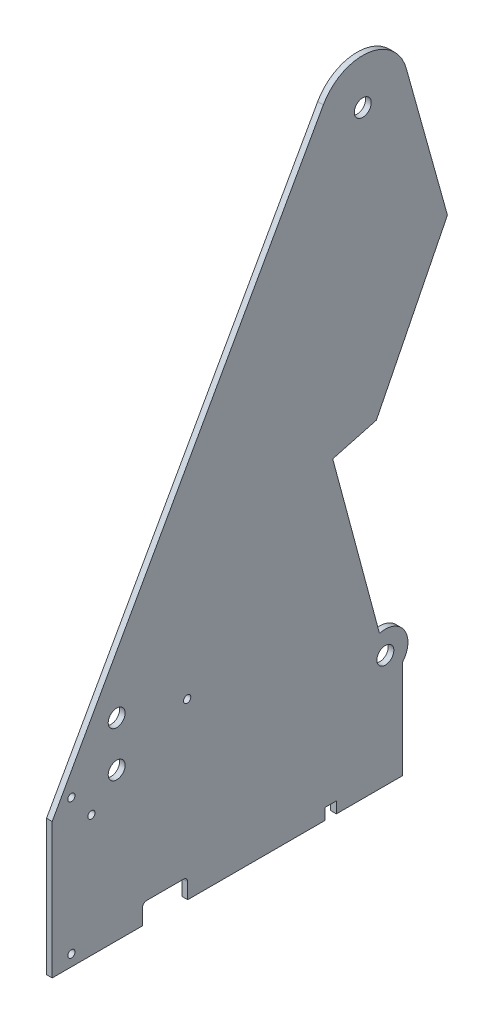
SolidWorks part; units mm, degrees
ref_plane "Front Plane" through (0, 0, 0) normal (0, 0, 1) x (1, 0, 0)
ref_plane "Top Plane" through (0, 0, 0) normal (0, 1, 0) x (1, 0, 0)
ref_plane "Right Plane" through (0, 0, 0) normal (1, 0, 0) x (0, 0, -1)
sketch "Sketch1" plane through (0, 0, 0) normal (1, 0, 0) x (0, 0, -1)
  line L0 (0, 0) -> (0, 55.0997)
  line L6 (-39.108, 173.9053) -> (-14.5735, 180.4793)
  line L7 (-14.5735, 180.4793) -> (25.4, 260.35)
  line L8 (25.4, 260.35) -> (2.241, 343.3746)
  line L9 (-44.3964, 348.943) -> (-196.85, 76.2)
  line L10 (-196.85, 0) -> (0, 0)
  line L11 (-196.85, 76.2) -> (-196.85, 0)
  line L13 (-39.108, 173.9053) -> (-12.812, 75.7673)
  line L14 (-12.812, 75.7673) -> (13.738, 82.8813) construction
  arc A0 (2.241, 343.3746) -> (-44.3964, 348.943) centre (-22.225, 336.55) ccw
  arc A3 (0, 55.0997) -> (-12.812, 75.7673) centre (-9.525, 63.5) ccw
  dimension "D2" = 25.4
  dimension "D6" = 196.85
  dimension "D7" = 76.2
  dimension "D12" = 12.7
  dimension "D1" = 22.225
  dimension "D3" = 336.55
  dimension "D4" = 25.4
  dimension "D5" = 101.6
  dimension "D10" = 9.525
  dimension "D11" = 63.5
  dimension "D13" = 76.2
  dimension "D14" = 25.4
  dimension "D15" = 15
extrude "Boss-Extrude1" add sketch "Sketch1" along normal blind 3.175
sketch "Sketch2" plane through (3.175, 0, 0) normal (1, 0, 0) x (0, 0, -1)
  line L16 (-146.05, 8.7909) -> (-146.05, -0.3034) construction
  line L17 (-123.0376, 11.1785) -> (-143.6624, 11.1785) construction
  line L18 (-120.65, -0.3034) -> (-120.65, 8.7909) construction
  line L19 (-146.05, 8.7909) -> (-146.05, 0)
  line L20 (-123.0376, 11.1785) -> (-143.6624, 11.1785)
  line L21 (-120.65, 0) -> (-120.65, 8.7909)
  line L23 (-37.0504, 0) -> (-37.0504, 6.35) construction
  line L24 (-43.4004, 0) -> (-37.0504, 0) construction
  line L25 (-146.05, 0) -> (-120.65, 0)
  line L26 (-196.85, 0) -> (0, 0) construction
  line L27 (-43.4004, 6.35) -> (-43.4004, 0) construction
  line L28 (-37.0504, 6.35) -> (-43.4004, 6.35) construction
  line L29 (-37.0504, 0) -> (-37.0504, 6.35)
  line L30 (-43.4004, 0) -> (-37.0504, 0)
  line L31 (-43.4004, 6.35) -> (-43.4004, 0)
  line L32 (-37.0504, 6.35) -> (-43.4004, 6.35)
  line L33 (-223.2996, 0) -> (-223.2996, 6.35) construction
  line L34 (-229.6496, 0) -> (-223.2996, 0) construction
  line L35 (-229.6496, 6.35) -> (-229.6496, 0) construction
  line L36 (-223.2996, 6.35) -> (-229.6496, 6.35) construction
  line L37 (-223.2996, 0) -> (-223.2996, 6.35)
  line L38 (-229.6496, 0) -> (-223.2996, 0)
  line L39 (-229.6496, 6.35) -> (-229.6496, 0)
  line L40 (-223.2996, 6.35) -> (-229.6496, 6.35)
  arc A0 (-143.6624, 11.1785) -> (-146.05, 8.7909) centre (-143.6624, 8.7909) ccw construction
  arc A1 (-120.65, 8.7909) -> (-123.0376, 11.1785) centre (-123.0376, 8.7909) ccw construction
  arc A2 (-143.6624, 11.1785) -> (-146.05, 8.7909) centre (-143.6624, 8.7909) ccw
  arc A3 (-120.65, 8.7909) -> (-123.0376, 11.1785) centre (-123.0376, 8.7909) ccw
extrude "Cut-Extrude1" cut sketch "Sketch2" against normal through all
sketch "Sketch3" plane through (3.175, 0, 0) normal (1, 0, 0) x (0, 0, -1)
  point P0 (-22.225, 336.55)
  point P4 (-9.525, 63.5)
hole_wizard "3/8 Clearance Hole1" positions "Sketch3" profile "Sketch4" hole size "3/8" standard "ANSI Inch" end condition up to next
sketch "Sketch4" plane through (3.175, 336.55, 22.225) normal (0, 1, 0) x (0, 0, -1)
  line L0 (0, 0) -> (0, 3.175)
  line L1 (0, 3.175) -> (4.7625, 3.175)
  line L2 (4.7625, 3.175) -> (4.7625, 0)
  line L5 (4.7625, 0) -> (0, 0)
  line L11 (0, -6.35) -> (0, 107.95) construction
  dimension "Thru Hole Dia." = 9.525
  dimension "Thru Hole Depth" = 3.175
sketch "Sketch5" [suppressed] plane through (3.175, 0, 0) normal (1, 0, 0) x (0, 0, -1)
  line L0 (-9.525, 63.5) -> (26.2895, 27.4728)
  line L1 (26.2895, 27.4728) -> (26.2524, 14.9296)
  line L2 (21.8127, 31.9762) -> (-24.8224, 22.3166)
  line L3 (-15.875, 19.05) -> (-24.8224, 22.3166)
  line L4 (0, 0) -> (0, 55.0997) construction
  line L5 (-15.875, 19.05) -> (-33.1481, 11.0161)
  line L6 (-33.1481, 11.0161) -> (-54.7505, 169.5016)
  line L7 (50.8, 0) -> (50.8, 73.5762) construction
  dimension "D1" = 44.45
  dimension "D2" = 50.8
  dimension "D3" = 45
  dimension "D4" = 60.325
  dimension "D5" = 19.05
  dimension "D6" = 15.875
  dimension "D7" = 9.525
  dimension "D8" = 47.625
  dimension "D9" = 19.05
  dimension "D10" = 45
  dimension "D11" = 50.8
sketch "Sketch6" plane through (3.175, 0, 0) normal (1, 0, 0) x (0, 0, -1)
  line L1 (-160.5832, 108.5458) -> (-174.4403, 116.2915) construction
  line L3 (-44.3964, 348.943) -> (-196.85, 76.2) construction
  circle A2 centre (-160.5832, 108.5458) radius 4.7625
  dimension "D4" = 9.525
  dimension "D5" = 15.875
  dimension "D6" = 266.7
extrude "Cut-Extrude2" cut sketch "Sketch6" against normal through all
sketch "Sketch8" plane through (3.175, 0, 0) normal (1, 0, 0) x (0, 0, -1)
  circle A0 centre (-160.5832, 83.1458) radius 4.7625
  circle A1 centre (-174.8072, 68.4138) radius 2.032
  circle A2 centre (-120.9592, 97.8778) radius 2.032
  circle A3 centre (-174.8072, 68.4138) radius 1.905 construction
  circle A4 centre (-120.9592, 97.8778) radius 1.985 construction
  dimension "D1" = 25.4
  dimension "D2" = 9.525
  dimension "D3" = 4.064
extrude "Cut-Extrude3" cut sketch "Sketch8" against normal through all both and the other way through all
sketch "Sketch9" plane through (3.175, 0, 0) normal (1, 0, 0) x (0, 0, -1)
  circle A8 centre (-174.8072, 68.4138) radius 4.445
  circle A9 centre (-174.8072, 68.4138) radius 4.445
  dimension "D1" = 2.54
sketch "Sketch10" [suppressed] plane through (3.175, 0, 0) normal (1, 0, 0) x (0, 0, -1)
  circle A0 centre (-71.2566, 151.9429) radius 2.032
  dimension "D1" = 4.064
extrude "Cut-Extrude4" [suppressed] cut sketch "Sketch10" against normal through all
sketch "Sketch11" plane through (3.175, 0, 0) normal (1, 0, 0) x (0, 0, -1)
  circle A0 centre (-186.055, 82.4979) radius 2.032
  circle A1 centre (-186.055, 6.35) radius 2.032
  circle A2 centre (-186.055, 6.35) radius 2.032 construction
  circle A3 centre (-186.055, 82.4979) radius 2.032 construction
  dimension "D1" = 4.064
extrude "Cut-Extrude5" cut sketch "Sketch11" against normal through all
sketch "Sketch13" [suppressed] plane through (0, 0, 0) normal (-1, 0, 0) x (0, 0, 1)
  circle A0 centre (31.5283, 339.7286) radius 2.032
  circle A1 centre (36.1757, 331.4144) radius 2.032
  dimension "D1" = 4.064
extrude "Cut-Extrude6" [suppressed] cut sketch "Sketch13" against normal through all
sketch "Sketch14" [suppressed] plane through (3.175, 0, 0) normal (1, 0, 0) x (0, 0, -1)
  line L0 (-44.3964, 348.943) -> (-196.85, 76.2) construction
  line L1 (-127, 181.6415) -> (-135.3143, 186.2888) construction
  circle A0 centre (-127, 181.6415) radius 2.032
  dimension "D1" = 4.064
  dimension "D2" = 9.525
  dimension "D3" = 127
extrude "Cut-Extrude7" [suppressed] cut sketch "Sketch14" against normal through all
sketch "Sketch15" [suppressed] plane through (3.175, 0, 0) normal (1, 0, 0) x (0, 0, -1)
  circle A0 centre (-120.6571, 192.989) radius 3.4925
  circle A2 centre (-120.6571, 192.989) radius 2.415 construction
  dimension "D1" = 6.985
extrude "Cut-Extrude8" [suppressed] cut sketch "Sketch15" against normal through all
